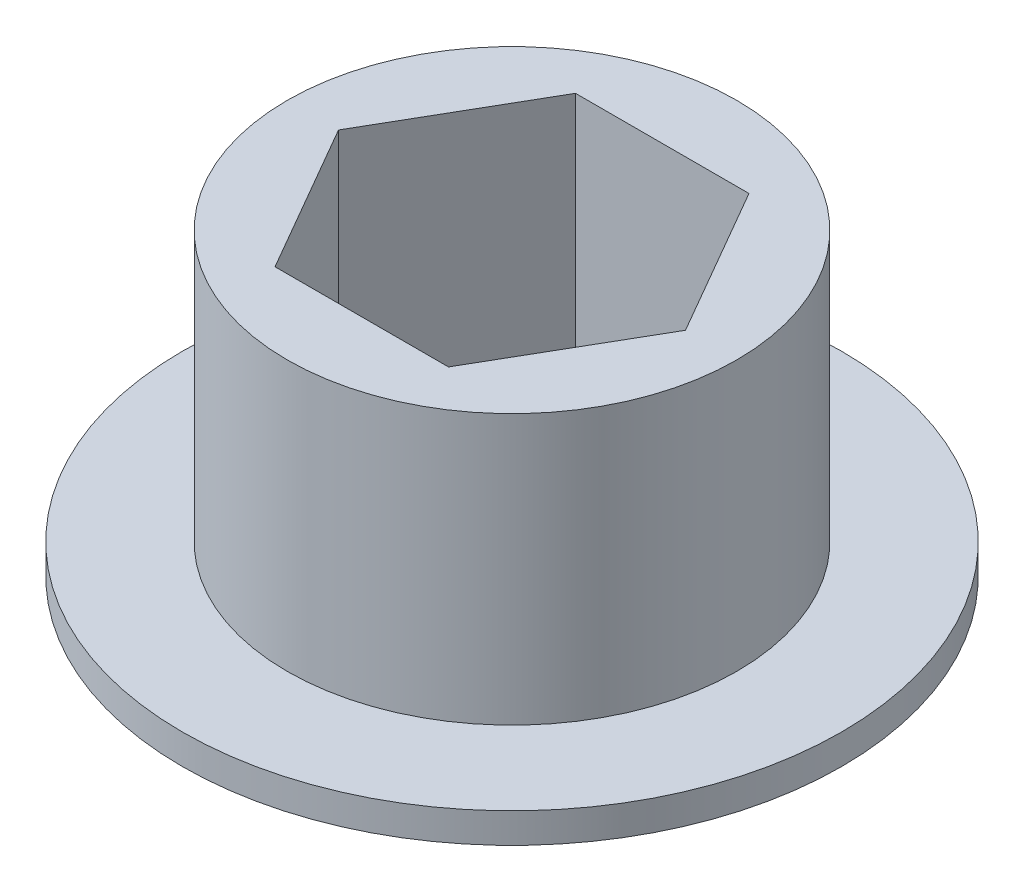
SolidWorks part; units mm, degrees
ref_plane "Front Plane" through (0, 0, 0) normal (0, 0, 1) x (1, 0, 0)
ref_plane "Top Plane" through (0, 0, 0) normal (0, 1, 0) x (1, 0, 0)
ref_plane "Right Plane" through (0, 0, 0) normal (1, 0, 0) x (0, 0, -1)
sketch "Sketch1" plane through (0, 0, 0) normal (0, 1, 0) x (1, 0, 0)
  line L0 (-2.894, -5.0125) -> (2.894, -5.0125)
  line L1 (2.894, -5.0125) -> (5.7879, 0)
  line L2 (5.7879, 0) -> (2.894, 5.0125)
  line L3 (2.894, 5.0125) -> (-2.894, 5.0125)
  line L4 (-2.894, 5.0125) -> (-5.7879, 0)
  line L5 (-5.7879, 0) -> (-2.894, -5.0125)
  circle A0 centre (0, 0) radius 7.5
  point P7 (0, 0)
  point P9 (0, 5.0125)
  dimension "D3" = 15
  dimension "D1" = 120
  dimension "D2" = 10.025
extrude "Boss-Extrude1" add sketch "Sketch1" along normal mid plane 10
ref_axis "Axis1" through (0, 0, 0) along (0, 1, 0)
sketch "Sketch2" plane through (0, -5, 0) normal (0, -1, 0) x (1, 0, 0)
  circle A0 centre (0, 0) radius 11
  circle A1 centre (0, 0) radius 7.5
  circle A2 centre (0, 0) radius 7.5 construction
  dimension "D1" = 3.5
extrude "Boss-Extrude2" add sketch "Sketch2" against normal blind 1
